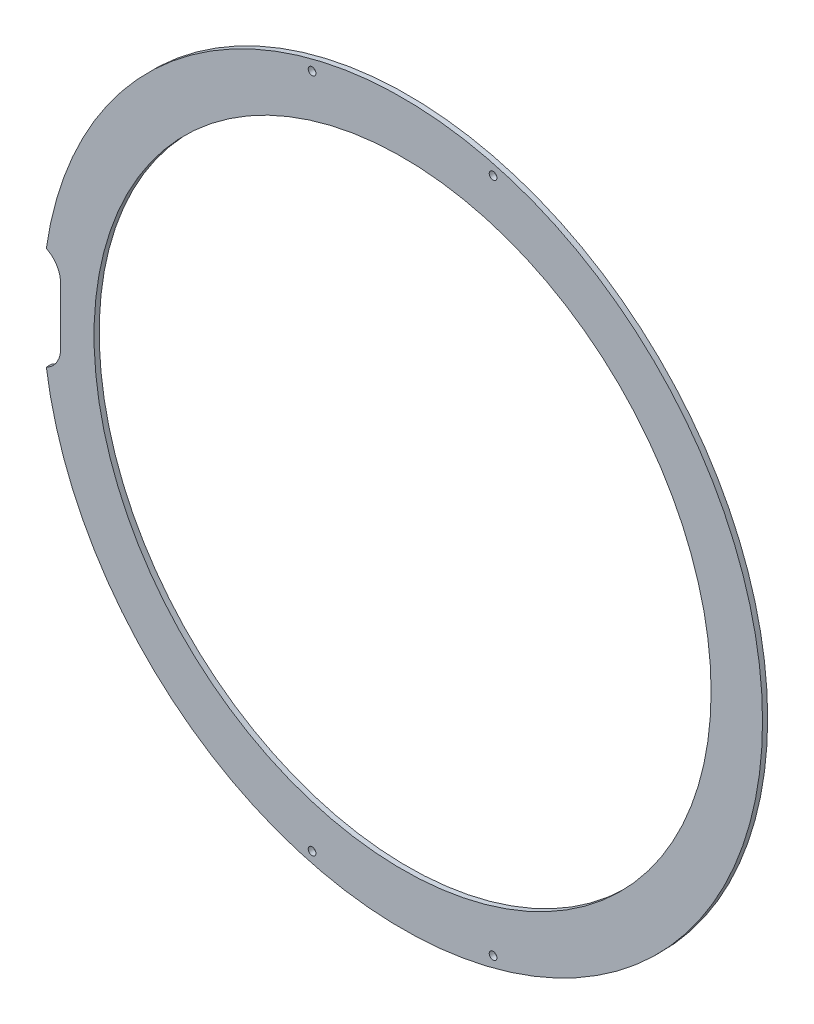
SolidWorks part; units mm, degrees
ref_plane "Plan de face" through (0, 0, 0) normal (0, 0, 1) x (1, 0, 0)
ref_plane "Plan de dessus" through (0, 0, 0) normal (0, 1, 0) x (1, 0, 0)
ref_plane "Plan de droite" through (0, 0, 0) normal (1, 0, 0) x (0, 0, -1)
sketch "Esquisse1" plane through (0, 0, 0) normal (0, 0, 1) x (1, 0, 0)
  circle A0 centre (0, 0) radius 140
  circle A1 centre (0, 0) radius 120
extrude "Boss.-Extru.1" add sketch "Esquisse1" along normal blind 2
sketch "Esquisse2" plane through (0, 0, 2) normal (0, 0, 1) x (1, 0, 0)
  line L5 (-143, -20) -> (-133, -20)
  line L6 (-143, -20) -> (-143, 20)
  line L7 (-143, 20) -> (-133, 20)
  line L8 (-133, -20) -> (-133, 20)
  dimension "D2" = 40
  dimension "D7" = 20
  dimension "D15" = 143
  dimension "D16" = 10
extrude "Enlèv. mat.-Extru.1" cut sketch "Esquisse2" against normal up to next
sketch "Esquisse4" plane through (0, 0, 2) normal (0, 0, 1) x (1, 0, 0)
  line L1 (-133, -20) -> (-121.3631, -20)
  line L2 (-133, -20) -> (-133, 40)
  line L3 (-133, 40) -> (-121.3631, 40)
  line L4 (-121.3631, -20) -> (-121.3631, 40)
  circle A0 centre (0, 0) radius 120 construction
  dimension "D1" = 60
  dimension "D2" = 123
extrude "Boss.-Extru.2" add sketch "Esquisse4" against normal blind 2
fillet "Congé1" radius 10 2 edges at (-133, -20, 1) (-133, 20, 1)
sketch "Esquisse5" plane through (0, 0, 2) normal (0, 0, 1) x (1, 0, 0)
  line L0 (0, 0) -> (-12940.9523, -48296.2913) construction
  line L1 (0, 0) -> (12940.9523, -48296.2913) construction
  circle A0 centre (-35.1994, -131.3659) radius 1.5
  circle A1 centre (35.1994, -131.3659) radius 1.5
  circle A2 centre (-35.1994, 131.3659) radius 1.5
  circle A3 centre (35.1994, 131.3659) radius 1.5
  dimension "D1" = 136
  dimension "D2" = 136
  dimension "D3" = 136
  dimension "D4" = 136
extrude "Enlèv. mat.-Extru.2" cut sketch "Esquisse5" against normal up to next
